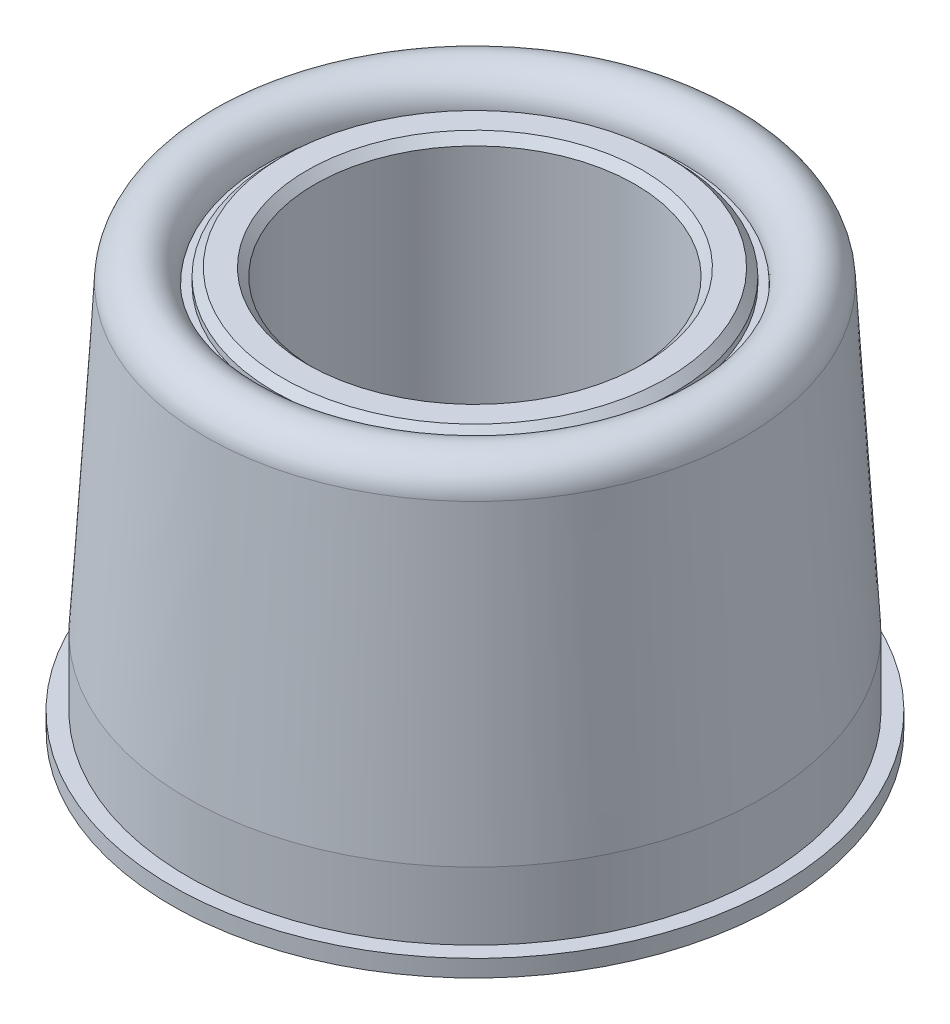
SolidWorks part; units mm, degrees
note: '?' marks a value the reader was unsure of.
ref_plane "Front Plane" through (0, 0, 0) normal (0, 0, 1) x (1, 0, 0)
ref_plane "Top Plane" through (0, 0, 0) normal (0, 1, 0) x (1, 0, 0)
ref_plane "Right Plane" through (0, 0, 0) normal (1, 0, 0) x (0, 0, -1)
sketch "Sketch1" plane through (0, 0, 0) normal (0, 0, 1) x (1, 0, 0)
  line L0 (0, -9.0424) -> (0, 9.0424) construction
  line L1 (-7.515, 9.0424) -> (7.515, 9.0424)
  line L2 (-14.25, -9.8) -> (-14.25, -9)
  line L3 (-14.25, -9) -> (14.25, -9)
  line L4 (14.25, -9) -> (14.25, -9.8)
  line L5 (14.25, -9.8) -> (-14.25, -9.8)
  line L6 (-13.49, -9) -> (-13.49, -5.825)
  line L7 (-13.49, -5.825) -> (13.49, -5.825)
  line L8 (13.49, -5.825) -> (13.49, -9)
  line L9 (-13.49, -5.825) -> (-12.5617, 9.8)
  line L10 (-12.5617, 9.8) -> (12.5617, 9.8)
  line L11 (12.5617, 9.8) -> (13.49, -5.825)
  line L12 (-7.515, 9.0424) -> (-9.4, 9.0424) construction
  line L13 (-9.4, 9.0424) -> (-9.4, -9.0424)
  line L14 (-9.4, -9.0424) -> (9.4, -9.0424) construction
  line L15 (7.515, 9.0424) -> (9.4, 9.0424) construction
  line L16 (9.4, -9.0424) -> (9.4, 9.0424)
  line L17 (-9.78, 9.8) -> (-9.78, -9.8) construction
  line L18 (9.78, 9.8) -> (9.78, -9.8) construction
  line L19 (-9.78, 8.3679) -> (-9.4, 8.3679)
  line L20 (0, -9.8) -> (0, 9.8) construction
  line L21 (0, 9.8) -> (0, -9.8) construction
  arc A0 (-9.78, 8.3679) -> (-12.6417, 8.4528) centre (-11.2121, 8.3679) ccw
  point P7 (0, -9.8)
  point P13 (0, -5.825)
  point P17 (0, 9.8)
  point P28 (0, 0)
  point P33 (0, -9.8324)
  point P34 (0, -8.2524)
  point P35 (0, 0)
ref_plane "Plane1" through (0, -9.8324, 0) normal (0, 1, 0) x (1, 0, 0)
ref_plane "Plane2" through (0, -8.2524, 0) normal (0, 1, 0) x (1, 0, 0)
sketch "Sketch2" plane through (0, 0, 0) normal (0, 0, 1) x (1, 0, 0)
  line L0 (-14.25, -9.8) -> (-14.25, -9)
  line L1 (-14.25, -9) -> (-13.49, -9)
  line L2 (-13.49, -9) -> (-13.49, -5.825)
  line L3 (-13.49, -5.825) -> (-12.6417, 8.4528)
  line L8 (-9.78, -9.8) -> (-14.25, -9.8)
  line L9 (-9.78, 8.3679) -> (-9.78, -9.8)
  arc A0 (-9.78, 8.3679) -> (-12.6417, 8.4528) centre (-11.2121, 8.3679) ccw construction
  arc A1 (-9.78, 8.3679) -> (-12.6417, 8.4528) centre (-11.2121, 8.3679) ccw
revolve "Outer" add sketch "Sketch2" angle 360 about L0
sketch "Sketch3" plane through (0, 0, 0) normal (0, 0, 1) x (1, 0, 0)
  line L0 (-9.4, 9.0424) -> (-9.4, -9.0424)
  line L1 (-9.4, -9.0424) -> (-7.515, -9.0424)
  line L2 (-9.4, -9.0424) -> (9.4, -9.0424) construction
  line L3 (-7.515, -9.0424) -> (-7.515, 9.0424)
  line L4 (-7.515, 9.0424) -> (-9.4, 9.0424)
revolve "Inner" add sketch "Sketch3" angle 360 about L0
chamfer "Chamfer1" distance 0.3757 angle 45 4 edges at (0, -9.0424, -9.4) (0, 9.0424, -9.4) (0, -9.0424, -7.515) (0, 9.0424, -7.515)
move or copy body "Style 1" [suppressed] bodies to move or copy 104 placed by mates yes
move or copy body "Style 2" bodies to move or copy 104 placed by mates yes
sketch "Sketch4" plane through (0, 0, 0) normal (0, 0, 1) x (1, 0, 0)
  line L0 (-9.78, 8.3679) -> (-9.4, 8.3679)
  line L1 (-9.4, 8.3679) -> (-9.4, -9)
  line L2 (-9.4, 9.0424) -> (-9.4, -9.0424) construction
  line L3 (-9.4, -9) -> (-9.78, -9)
  line L5 (-9.78, -9) -> (-9.78, 8.3679)
  line L9 (-14.25, -9) -> (-9.78, -9) construction
  line L10 (14.25, -9) -> (-14.25, -9) construction
  line L11 (-14.25, -9.8) -> (-14.25, -9) construction
revolve "Combine" add sketch "Sketch4" angle 360 about L0
ref_axis "Center Axis 1" through (0, 8.6666, 0) along (0, -1, 0)?
ref_plane "Contact Plane 1" through (0, 9.0424, 0) normal (0, 1, 0) x (1, 0, 0)
ref_plane "Contact Plane 2" through (0, -9.0424, 0) normal (0, -1, 0) x (-1, 0, 0)
ref_plane "Contact Plane 3" through (0, -9.8, 0) normal (0, -1, 0) x (-1, 0, 0)
ref_plane "Contact Plane 4" through (0, 9.8, 0) normal (0, -1, 0) x (-1, 0, 0)
equation "\"D1@Chamfer1\"=.025*\"ID@Sketch1\""
equation "\"D1@Contact Plane 4\" = \"Outer Length@Sketch1\""
